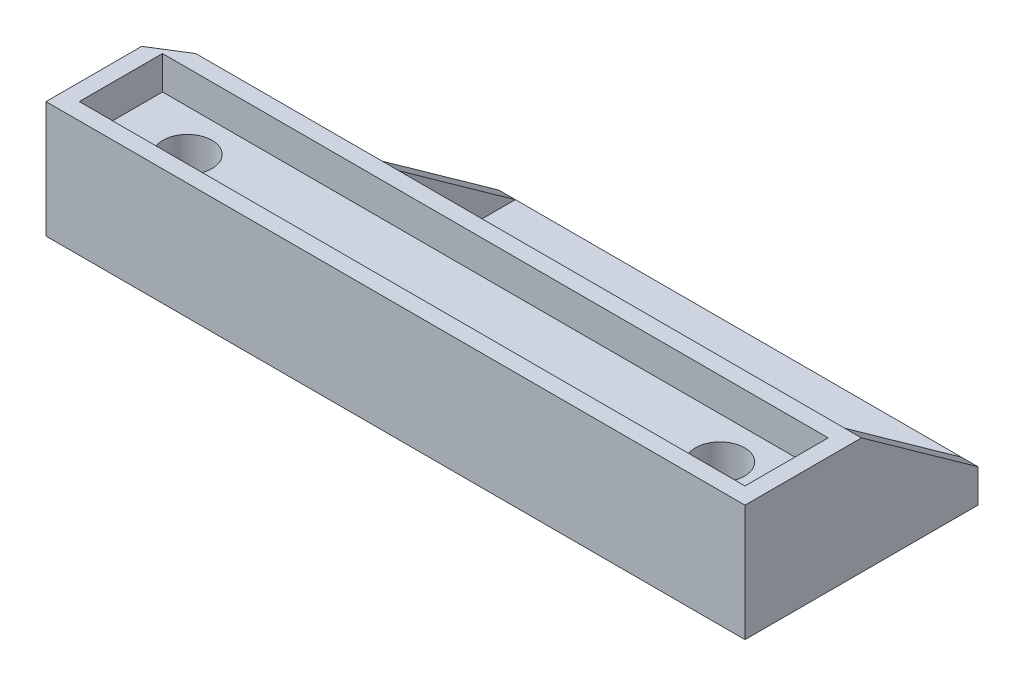
SolidWorks part; units mm, degrees
ref_plane "Front Plane" through (0, 0, 0) normal (0, 0, 1) x (1, 0, 0)
ref_plane "Top Plane" through (0, 0, 0) normal (0, 1, 0) x (1, 0, 0)
ref_plane "Right Plane" through (0, 0, 0) normal (1, 0, 0) x (0, 0, -1)
sketch "Sketch1" plane through (0, 0, 0) normal (0, 1, 0) x (1, 0, 0)
  line L1 (2.0004, 7) -> (42, 7)
  line L2 (0, 5.75) -> (0, 0)
  line L3 (0, 0) -> (42, 0)
  line L4 (42, 7) -> (42, 0)
  line L6 (0, 5.75) -> (2.0004, 7)
  dimension "D1" = 32
  dimension "D2" = 42
  dimension "D3" = 7
  dimension "D4" = 5.75
extrude "Riser" add sketch "Sketch1" along normal blind 7
sketch "Sketch2" plane through (0, 0, 0) normal (0, -1, 0) x (1, 0, 0)
  line L1 (21, 0) -> (21, -7) construction
  line L2 (0, 0) -> (42, 0) construction
  line L4 (42, -7) -> (2.0004, -7) construction
  line L5 (42, 0) -> (42, -7) construction
  circle A0 centre (37, -3.5) radius 1.475
  circle A2 centre (5, -3.5) radius 1.475
  point P2 (5, -3.3742)
  point P5 (36.5176, -3.4737)
  point P6 (42, -3.5)
  point P11 (20.6331, -7.3204)
  point P12 (0, 0)
  point P15 (5, -4.4257)
  dimension "D2" = 2.95
  dimension "D1" = 5
extrude "Mounting Holes" cut sketch "Sketch2" against normal through all
sketch "Sketch3" plane through (0, 7, 0) normal (0, 1, 0) x (1, 0, 0)
  line L5 (42, 7) -> (2.0004, 7) construction
  line L12 (1, 6) -> (41, 6)
  line L13 (1, 6) -> (1, 1)
  line L14 (1, 1) -> (41, 1)
  line L15 (41, 6) -> (41, 1)
  line L16 (42, 0) -> (42, 7) construction
  point P4 (0, 0)
  point P6 (5, 3.5)
  point P7 (0, 0)
  point P8 (0, 0)
  point P9 (37, 3.5)
  point P10 (0, 0)
  point P12 (0, 0)
  point P13 (0, 0)
  point P14 (0, 0)
  dimension "D1" = 5
  dimension "D2" = 40
  dimension "D3" = 1
  dimension "D4" = 1
extrude "Recess" cut sketch "Sketch3" against normal blind 2 contours L12 L15 L14 L13
sketch "Sketch4" plane through (0, 0, 0) normal (0, 1, 0) x (1, 0, 0)
  line L0 (-7.0926, 1.318) -> (28.8348, 23.768) construction
  line L1 (2.0004, 7) -> (42, 7)
  line L2 (42, 7) -> (42, 14)
  line L3 (42, 14) -> (13.2028, 14)
  line L4 (13.2028, 14) -> (2.0004, 7)
  point P8 (0, 0)
  point P10 (42, 14)
  point P11 (41.7666, 14)
  point P12 (0, 0)
  point P13 (0, 0)
  point P14 (42, 16.6341)
  point P15 (0, 0)
  dimension "D1" = 32
  dimension "D2" = 7
extrude "Flange" add sketch "Sketch4" along normal blind 7
sketch "Sketch5" plane through (0, 7, 0) normal (0, 1, 0) x (1, 0, 0)
  line L0 (14.2028, 7) -> (14.2028, 14)
  line L1 (42, 14) -> (13.2028, 14) construction
  line L2 (14.2028, 14) -> (41, 14)
  line L3 (41, 14) -> (41, 7)
  line L4 (41, 7) -> (14.2028, 7)
  line L5 (2.0004, 7) -> (13.2028, 7)
  line L6 (1, 6) -> (41, 6) construction
  line L7 (42, 0) -> (42, 14) construction
  line L8 (13.2028, 14) -> (0, 5.75) construction
  line L9 (13.2028, 7) -> (13.2028, 14)
  line L10 (13.2028, 14) -> (2.0004, 7)
  point P7 (0, 0)
  dimension "D2" = 1
  dimension "D3" = 1
  dimension "D4" = 1
extrude "Flange Cutout" cut sketch "Sketch5" against normal blind 5
sketch "Sketch7" plane through (41, 0, 0) normal (-1, 0, 0) x (0, 0, 1)
  line L0 (-7, 7) -> (-14, 2)
  line L1 (-14, 2) -> (-14, 7)
  line L2 (-14, 7) -> (-7, 7)
extrude "Angle Cutout" cut sketch "Sketch7" against normal through all and the other way through all
chamfer "Flange Chamfer 1" distance 1 angle 45 1 edges at (27.6014, 2, -7)
chamfer "Flange Chamfer 2" distance 1 angle 45 1 edges at (7.6016, 2, -7)
